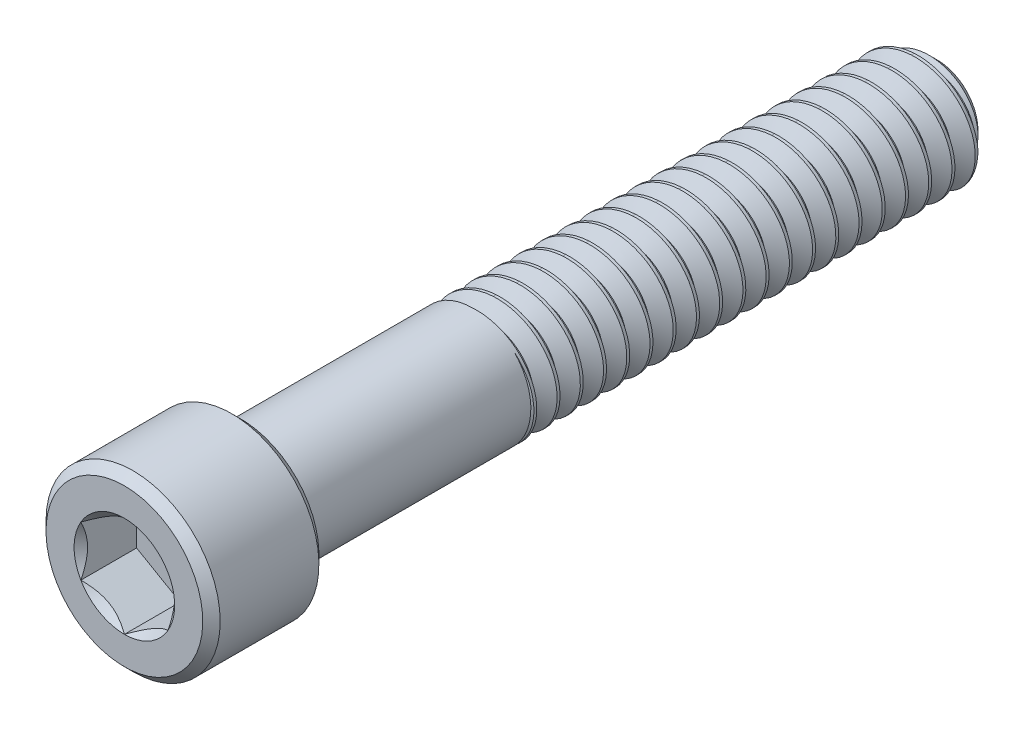
SolidWorks part; units mm, degrees
ref_plane "Front Plane" through (0, 0, 0) normal (0, 0, 1) x (1, 0, 0)
ref_plane "Top Plane" through (0, 0, 0) normal (0, 1, 0) x (1, 0, 0)
ref_plane "Right Plane" through (0, 0, 0) normal (1, 0, 0) x (0, 0, -1)
sketch "Sketch1" plane through (0, 0, 0) normal (1, 0, 0) x (0, 0, -1)
  line L0 (-22.225, 0) -> (22.225, 0) construction
  line L1 (-22.225, 0) -> (-22.225, 4.7625)
  line L2 (-22.225, 4.7625) -> (-15.875, 4.7625)
  line L3 (-15.875, 4.7625) -> (-15.875, 3.175)
  line L4 (-15.875, 3.175) -> (21.2725, 3.175)
  line L5 (22.1456, 3.3125) -> (22.7806, 2.2126) construction
  line L6 (22.7806, 2.2126) -> (23.4156, 3.3125) construction
  line L7 (23.4156, 3.3125) -> (22.1456, 3.3125) construction
  line L8 (21.2725, 3.175) -> (22.225, 2.2225)
  line L9 (22.225, 2.2225) -> (22.225, 0)
  line L10 (22.225, 3.175) -> (23.3363, 3.175) construction
  line L11 (22.7806, 3.3125) -> (22.7806, 3.175) construction
  line L12 (22.7806, 3.175) -> (22.7806, 2.3501) construction
  line L13 (22.7806, 2.3501) -> (22.7806, 2.2126) construction
  line L14 (22.7012, 2.3501) -> (22.86, 2.3501)
  line L15 (22.1853, 3.2437) -> (23.3759, 3.2437)
  line L16 (22.86, 2.3501) -> (23.3759, 3.2437)
  line L17 (22.7012, 2.3501) -> (22.1853, 3.2437)
  line L18 (-22.225, 2.3813) -> (-19.177, 2.3813)
  line L19 (-19.177, 2.3813) -> (-19.177, 0)
  line L20 (17.78, 3.175) -> (17.78, -3.175) construction
  point P20 (22.7806, 3.2437)
  point P22 (17.78, -3.175)
  point P23 (-3.175, 3.175)
  point P28 (17.78, 0)
  dimension "Head Diameter" = 9.525
  dimension "Length" = 38.1
  dimension "Head Height" = 6.35
  dimension "Screw Size Decimal Equivalent" = 6.35
  dimension "D1" = 45
  dimension "Thread Pitch" = 1.27
  dimension "D3" = 0.1588
  dimension "D2" = 0.9525
  dimension "Drive Size" = 4.7625
  dimension "Drive Depth" = 3.048
  dimension "Minimum Thread Length" = 25.4
  dimension "D4" = 4.445
sketch "Sketch3" plane through (0, 0, 0) normal (1, 0, 0) x (0, 0, -1)
  line L0 (-22.225, 4.7625) -> (-22.225, 2.3813)
  line L1 (-22.225, 2.3813) -> (-19.177, 2.3813)
  line L2 (-19.177, 2.3813) -> (-19.177, 0)
  line L3 (-19.177, 0) -> (22.225, 0)
  line L4 (22.225, 0) -> (22.225, 2.2225)
  line L5 (22.225, 2.2225) -> (21.2725, 3.175)
  line L6 (21.2725, 3.175) -> (-15.875, 3.175)
  line L7 (-15.875, 3.175) -> (-15.875, 4.7625)
  line L8 (-15.875, 4.7625) -> (-22.225, 4.7625)
revolve "Revolve1" add sketch "Sketch3" angle 360 about L0
sketch "Sketch4" plane through (0, 0, 22.225) normal (0, 0, 1) x (1, 0, 0)
  line L1 (0, 2.7496) -> (-2.3813, 1.3748)
  line L2 (-2.3813, 1.3748) -> (-2.3813, -1.3748)
  line L3 (-2.3813, -1.3748) -> (0, -2.7496)
  line L4 (0, -2.7496) -> (2.3813, -1.3748)
  line L5 (2.3813, -1.3748) -> (2.3813, 1.3748)
  line L6 (2.3813, 1.3748) -> (0, 2.7496)
  circle A0 centre (0, 0) radius 2.3813 construction
extrude "Cut-Extrude1" cut sketch "Sketch4" against normal up to vertex (3.048 mm away) up to point (0, 2.3813, 19.177)
sketch "Sketch5" plane through (0, 0, 22.225) normal (0, 0, 1) x (1, 0, 0)
  circle A0 centre (0, 0) radius 2.7496
extrude "Cut-Extrude2" cut sketch "Sketch5" against normal up to next (3.048 mm away) draft 45
chamfer "Chamfer1" distance 0.4763 angle 45 2 edges at (0, -4.7625, 15.875) (0, -4.7625, 22.225)
split "Split1" bodies to split 106 resulting bodies 107 108 split by face at (0, -4.2863, 15.875)
sketch "Sketch6" plane through (0, 0, -22.225) normal (0, 0, -1) x (-1, 0, 0)
  circle A0 centre (0, 0) radius 3.175 construction
  circle A1 centre (0, 0) radius 3.175
curve "Helix/Spiral1" pitch 1.27 height 39.37 radius 3.175 centre (0, 0, -22.225) axis (0, 0, 1) start towards (0, 1, 0)
sketch "Sketch7" plane through (0, 0, 0) normal (1, 0, 0) x (0, 0, -1)
  line L0 (22.7012, 2.3501) -> (22.86, 2.3501) construction
  line L1 (22.7012, 2.3501) -> (22.1853, 3.2437) construction
  line L2 (22.1853, 3.2437) -> (23.3759, 3.2437) construction
  line L3 (22.86, 2.3501) -> (23.3759, 3.2437) construction
  line L4 (22.7012, 2.3501) -> (22.86, 2.3501)
  line L5 (22.7012, 2.3501) -> (22.1853, 3.2437)
  line L6 (22.1853, 3.2437) -> (23.3759, 3.2437)
  line L7 (22.86, 2.3501) -> (23.3759, 3.2437)
sweep "Cut-Sweep1" cut profiles "Sketch7" path "Helix/Spiral1" align with end faces yes
sketch "Sketch8" plane through (0, 0, 15.875) normal (0, 0, -1) x (-1, 0, 0)
  circle A0 centre (0, 0) radius 3.4925
  point P3 (0, 3.4925)
  dimension "D1" = 0.3175
extrude "Boss-Extrude1" add sketch "Sketch8" along normal blind 2.54 draft 60
sketch "Sketch9" plane through (0, 0, 15.875) normal (0, 0, -1) x (-1, 0, 0)
  circle A0 centre (0, 0) radius 3.175
extrude "Boss-Extrude2" add sketch "Sketch9" along normal up to vertex (12.7 mm away) up to point (0, 3.175, 3.175)
equation "\"D3@Sketch1\" = \"Thread Pitch@Sketch1\" / 8"
equation "\"D2@Sketch1\" = \"Thread Pitch@Sketch1\" * .75"
equation "\"D4@Sketch1\" = \"Thread Pitch@Sketch1\" * 3.5"
equation "\"D1@Chamfer1\"=\"head diameter@sketch1\"*.05"
equation "\"D3@Helix/Spiral1\" = \"Length@Sketch1\" + \"Thread Pitch@Sketch1\""
equation "\"D4@Helix/Spiral1\" = \"Thread Pitch@Sketch1\""
equation "\"D1@Sketch8\" = \"Thread Pitch@Sketch1\" / 4"
